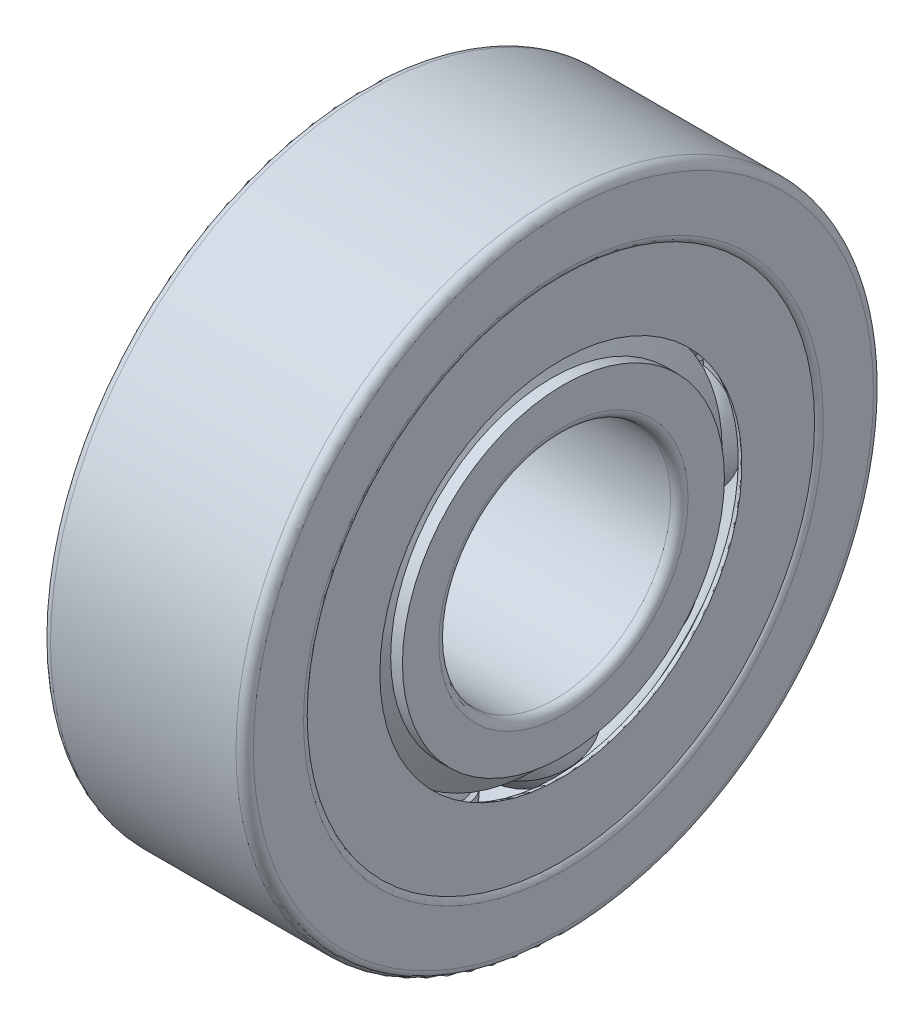
SolidWorks part; units mm, degrees
ref_plane "前视基准面" through (0, 0, 0) normal (0, 0, 1) x (1, 0, 0)
ref_plane "上视基准面" through (0, 0, 0) normal (0, 1, 0) x (1, 0, 0)
ref_plane "右视基准面" through (0, 0, 0) normal (1, 0, 0) x (0, 0, -1)
sketch "尺寸草图" plane through (0, 0, 0) normal (0, 0, 1) x (1, 0, 0)
  line L0 (-19.9271, 0) -> (19.9271, 0) construction
  line L1 (0, 21.603) -> (0, -21.603) construction
  line L2 (-3.2, 11) -> (3.2, 11)
  line L3 (3.5, 10.7) -> (3.5, 8.9667)
  line L4 (-3.5, 10.7) -> (-3.5, 8.9667)
  line L5 (-3.2, 8.6667) -> (3.2, 8.6667)
  line L6 (-3.5, 7.5) -> (3.3577, 7.5) construction
  line L7 (-3.2, 6.3333) -> (3.2, 6.3333)
  line L8 (3.5, 6.0333) -> (3.5, 4.3)
  line L9 (3.2, 4) -> (-3.2, 4)
  line L10 (-3.5, 4.3) -> (-3.5, 6.0333)
  line L11 (0, 7.5) -> (0, 9.25) construction
  line L13 (3.2, 8.6667) -> (3.2, 6.3333)
  line L14 (2.6444, 6.3333) -> (3.0935, 5.5556)
  line L15 (3.0935, 5.5556) -> (3.5, 5.5556)
  line L16 (3.4121, 8.7545) -> (3.4121, 6.2455)
  circle A0 centre (0, 7.5) radius 1.75
  arc A1 (3.5, 8.9667) -> (3.2, 8.6667) centre (3.2, 8.9667) cw
  arc A2 (3.5, 6.0333) -> (3.2, 6.3333) centre (3.2, 6.0333) ccw
  arc A3 (-3.2, 6.3333) -> (-3.5, 6.0333) centre (-3.2, 6.0333) ccw
  arc A4 (-3.2, 8.6667) -> (-3.5, 8.9667) centre (-3.2, 8.9667) cw
  arc A5 (-3.2, 4) -> (-3.5, 4.3) centre (-3.2, 4.3) cw
  arc A6 (3.2, 4) -> (3.5, 4.3) centre (3.2, 4.3) ccw
  arc A7 (3.5, 10.7) -> (3.2, 11) centre (3.2, 10.7) ccw
  arc A8 (-3.2, 11) -> (-3.5, 10.7) centre (-3.2, 10.7) ccw
  point P7 (0, 0)
  point P25 (-3.5, 6.3333)
  point P28 (-3.5, 8.6667)
  point P31 (-3.5, 4)
  point P36 (3.5, 11)
  point P39 (-3.5, 11)
  dimension "D1" = 0.5833
  dimension "D3" = 0.3
  dimension "B" = 7
  dimension "D2" = 3.5
  dimension "D" = 22
  dimension "(d)" = 8
  dimension "D5" = 7.5
  dimension "D6" = 2.3333
  dimension "D7" = 2.3333
  dimension "D8" = 0.7778
  dimension "D9" = 60
  dimension "D10" = 0.8556
sketch "草图2" plane through (0, 0, 0) normal (0, 0, 1) x (1, 0, 0)
  line L0 (2.6444, 6.3333) -> (3.0935, 5.5556) construction
  line L1 (3.0935, 5.5556) -> (3.5, 5.5556) construction
  line L2 (2.6444, 6.3333) -> (3.0935, 5.5556)
  line L3 (3.0935, 5.5556) -> (3.5, 5.5556)
  line L4 (0, 9.25) -> (0, 5.75) construction
  line L5 (-3.0935, 5.5556) -> (-3.5, 5.5556)
  line L6 (3.2, 4) -> (-3.2, 4) construction
  line L7 (-2.6444, 6.3333) -> (-3.0935, 5.5556)
  line L8 (-3.5, 10.7) -> (-3.5, 8.9667) construction
  line L9 (-3.2, 8.6667) -> (3.2, 8.6667) construction
  line L10 (-3.2, 11) -> (3.2, 11) construction
  line L11 (3.5, 10.7) -> (3.5, 8.9667) construction
  line L12 (3.5, 6.0333) -> (3.5, 4.3) construction
  line L13 (-3.2, 6.3333) -> (3.2, 6.3333) construction
  line L14 (3.2, 4) -> (-3.2, 4)
  line L15 (-3.5, 4.3) -> (-3.5, 6.0333) construction
  line L18 (-3.5, 0) -> (3.5, 0) construction
  line L19 (-19.9271, 0) -> (19.9271, 0) construction
  line L20 (-3.5, 10.7) -> (-3.5, 8.9667)
  line L21 (-3.2, 8.6667) -> (-1.3044, 8.6667)
  line L22 (-3.2, 11) -> (3.2, 11)
  line L23 (3.5, 10.7) -> (3.5, 8.9667)
  line L24 (3.5, 5.5556) -> (3.5, 4.3)
  line L25 (-2.6444, 6.3333) -> (-1.3044, 6.3333)
  line L26 (-3.5, 4.3) -> (-3.5, 5.5556)
  line L27 (1.3044, 8.6667) -> (3.2, 8.6667)
  line L28 (1.3044, 6.3333) -> (2.6444, 6.3333)
  circle A0 centre (0, 7.5) radius 1.75 construction
  arc A1 (1.3044, 8.6667) -> (-1.3044, 8.6667) centre (0, 7.5) ccw
  arc A2 (-1.3044, 6.3333) -> (1.3044, 6.3333) centre (0, 7.5) ccw
  arc A3 (-3.2, 11) -> (-3.5, 10.7) centre (-3.2, 10.7) ccw construction
  arc A4 (-3.5, 8.9667) -> (-3.2, 8.6667) centre (-3.2, 8.9667) ccw construction
  arc A5 (3.5, 10.7) -> (3.2, 11) centre (3.2, 10.7) ccw construction
  arc A6 (3.2, 8.6667) -> (3.5, 8.9667) centre (3.2, 8.9667) ccw construction
  arc A8 (3.2, 4) -> (3.5, 4.3) centre (3.2, 4.3) ccw construction
  arc A10 (-3.5, 4.3) -> (-3.2, 4) centre (-3.2, 4.3) ccw construction
  arc A11 (-3.2, 11) -> (-3.5, 10.7) centre (-3.2, 10.7) ccw
  arc A12 (-3.5, 8.9667) -> (-3.2, 8.6667) centre (-3.2, 8.9667) ccw
  arc A13 (3.5, 10.7) -> (3.2, 11) centre (3.2, 10.7) ccw
  arc A14 (3.2, 8.6667) -> (3.5, 8.9667) centre (3.2, 8.9667) ccw
  arc A16 (3.2, 4) -> (3.5, 4.3) centre (3.2, 4.3) ccw
  arc A18 (-3.5, 4.3) -> (-3.2, 4) centre (-3.2, 4.3) ccw
revolve "旋转1" add sketch "草图2" angle 360 about L18
sketch "草图5" plane through (0, 0, 0) normal (0, 0, 1) x (1, 0, 0)
  line L1 (-0.525, 7.15) -> (0.525, 7.15)
  line L2 (-0.525, 7.15) -> (-0.525, 7.85)
  line L3 (-0.525, 7.85) -> (0.525, 7.85)
  line L4 (0.525, 7.15) -> (0.525, 7.85)
  line L5 (-0.525, 7.15) -> (0.525, 7.85) construction
  line L6 (-0.525, 7.85) -> (0.525, 7.15) construction
  circle A0 centre (0, 7.5) radius 1.75 construction
  circle A1 centre (0, 7.5) radius 1.75 construction
  point P0 (0, 7.5)
  dimension "D3" = 3.5
  dimension "D1" = 1.05
  dimension "D2" = 0.7
revolve "旋转3" add sketch "草图5" angle 360 about L0
sketch "草图3" plane through (0, 0, 0) normal (0, 0, 1) x (1, 0, 0)
  line L1 (-1.925, 7.5) -> (1.925, 7.5)
  circle A0 centre (0, 7.5) radius 1.75 construction
  circle A1 centre (0, 7.5) radius 1.75 construction
  arc A2 (1.925, 7.5) -> (-1.925, 7.5) centre (0, 7.5) ccw
  dimension "D2" = 3.85
revolve "旋转2" add sketch "草图3" angle 360 about L1 region at (0, 8.317, 0)
ref_axis "基准轴1" through (-3.85, 0, 0) along (1, 0, 0)
pattern_circular "阵列(圆周)5" count 11 over 360 about axis through (-3.85, 0, 0) along (1, 0, 0) of bodies 103
sketch "草图6" plane through (0, 0, 0) normal (0, 0, 1) x (1, 0, 0)
  line L0 (-1.8929, 7.85) -> (1.8929, 7.85)
  line L1 (-3.5, 7.5) -> (3.5, 7.5) construction
  line L3 (-1.8929, 7.15) -> (1.8929, 7.15)
  line L4 (3.5, -10.7) -> (3.5, 10.7) construction
  arc A0 (-1.8929, 7.15) -> (1.8929, 7.15) centre (0, 7.5) ccw
  circle A1 centre (0, 7.5) radius 1.75 construction
  circle A2 centre (0, 7.5) radius 1.75 construction
  arc A3 (1.8929, 7.85) -> (-1.8929, 7.85) centre (0, 7.5) ccw
  dimension "D1" = 3.85
  dimension "D2" = 3.5
  dimension "D3" = 0.35
  dimension "D4" = 0.35
revolve "切除-旋转1" cut sketch "草图6" angle 360 about L0
sketch "草图7" plane through (0, 0, 0) normal (0, 0, 1) x (1, 0, 0)
  line L0 (-1.75, 7.5) -> (1.75, 7.5)
  line L1 (-3.5, 0) -> (2.4587, 0) construction
  line L2 (-3.5, 10.7) -> (-3.5, -10.7) construction
  line L3 (-19.9271, 0) -> (19.9271, 0) construction
  circle A0 centre (0, 7.5) radius 1.75 construction
  arc A1 (1.75, 7.5) -> (-1.75, 7.5) centre (0, 7.5) ccw
revolve "旋转4" add sketch "草图7" angle 360 about L0
pattern_circular "阵列(圆周)2" count 11 over 360 about axis through (-3.85, 0, 0) along (1, 0, 0) of "旋转4" reverse direction yes
sketch "草图9" plane through (0, 0, 0) normal (0, 0, 1) x (1, 0, 0)
  line L1 (3.2, 8.6667) -> (3.2, 6.3333) construction
  line L4 (3.4121, 8.7545) -> (3.4121, 6.2455) construction
  line L5 (3.2, 8.6667) -> (3.2, 6.3333)
  line L6 (3.4121, 8.7545) -> (3.4121, 6.2455)
  line L7 (-3.4121, 8.7545) -> (-3.4121, 6.2455)
  line L8 (0, 11) -> (0, 0) construction
  line L9 (-3.2, 11) -> (3.2, 11) construction
  line L10 (-3.2, 8.6667) -> (-3.2, 6.3333)
  arc A0 (3.2, 8.6667) -> (3.5, 8.9667) centre (3.2, 8.9667) ccw construction
  arc A1 (3.2, 8.6667) -> (3.4121, 8.7545) centre (3.2, 8.9667) ccw
  arc A2 (3.5, 6.0333) -> (3.2, 6.3333) centre (3.2, 6.0333) ccw construction
  arc A3 (3.4121, 6.2455) -> (3.2, 6.3333) centre (3.2, 6.0333) ccw
  arc A4 (-3.4121, 6.2455) -> (-3.2, 6.3333) centre (-3.2, 6.0333) cw
  arc A5 (-3.2, 8.6667) -> (-3.4121, 8.7545) centre (-3.2, 8.9667) cw
revolve "旋转5" add sketch "草图9" angle 360 about L0
